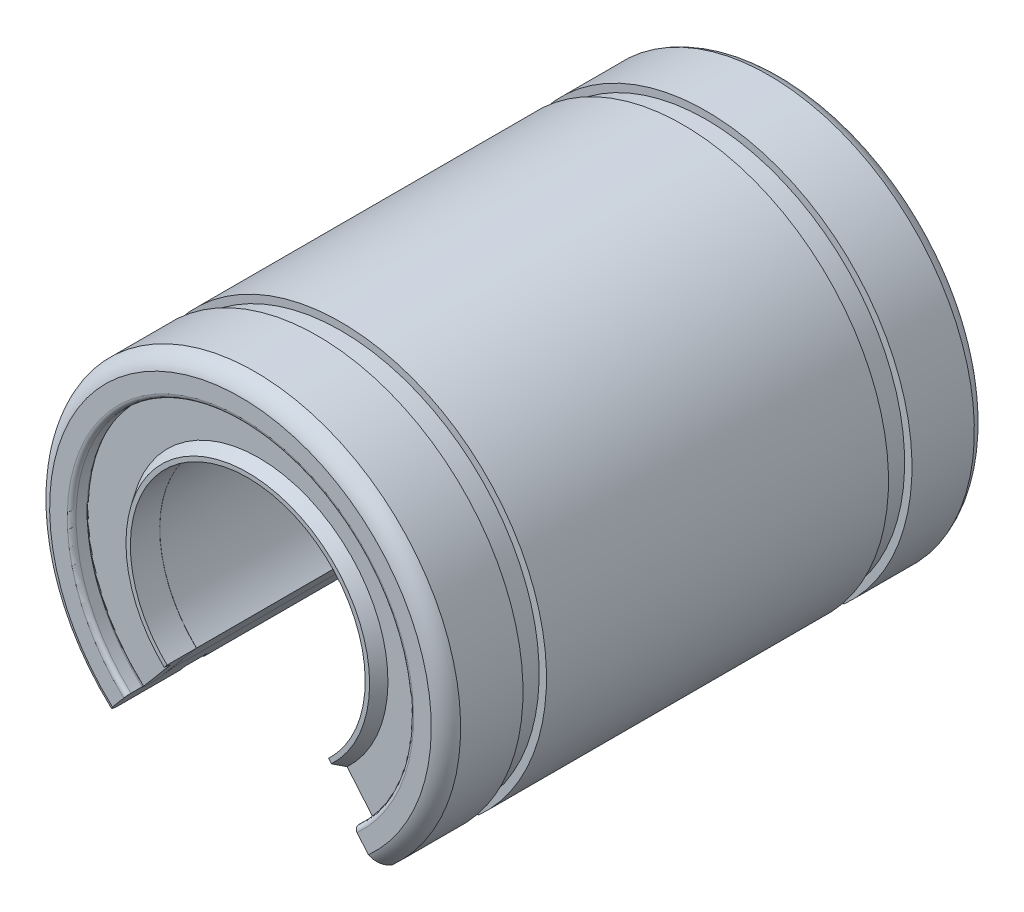
SolidWorks part; units mm, degrees
ref_plane "Спереди" through (0, 0, 0) normal (0, 0, 1) x (1, 0, 0)
ref_plane "Сверху" through (0, 0, 0) normal (0, 1, 0) x (1, 0, 0)
ref_plane "Справа" through (0, 0, 0) normal (1, 0, 0) x (0, 0, -1)
sketch "Эскиз1" plane through (0, 0, 0) normal (1, 0, 0) x (0, 0, -1)
  line L0 (-43.3432, 0) -> (33.9644, 0) construction
  line L1 (0, 8) -> (0, 0) construction
  line L2 (-18.5, 14) -> (18.5, 14)
  line L3 (-18.5, 14) -> (-18.5, 8)
  line L4 (-18.5, 8) -> (18.5, 8)
  line L5 (18.5, 14) -> (18.5, 8)
  line L6 (-11.65, 13.5) -> (11.65, 13.5) construction
  line L7 (-13.25, 14) -> (-11.65, 14)
  line L8 (-13.25, 14) -> (-13.25, 13.5)
  line L9 (-13.25, 13.5) -> (-11.65, 13.5)
  line L10 (-11.65, 14) -> (-11.65, 13.5)
  line L11 (11.65, 14) -> (13.25, 14)
  line L12 (11.65, 14) -> (11.65, 13.5)
  line L13 (11.65, 13.5) -> (13.25, 13.5)
  line L14 (13.25, 14) -> (13.25, 13.5)
  line L15 (0, 8) -> (0, 13.5) construction
  line L16 (-18.5, 11) -> (18.5, 11)
  line L17 (-17.25, 11.5) -> (-18.5, 11.5)
  line L18 (-17.25, 11) -> (-16, 11)
  line L19 (-17.25, 11) -> (-17.25, 12)
  line L20 (-17.25, 12) -> (-16, 12)
  line L21 (-16, 11) -> (-16, 12)
  line L22 (17.25, 11) -> (16, 11)
  line L23 (17.25, 11) -> (17.25, 12)
  line L24 (17.25, 12) -> (16, 12)
  line L25 (16, 11) -> (16, 12)
  line L26 (17.25, 11.5) -> (18.5, 11.5)
  line L27 (17.25, 11) -> (17.25, 8.8)
  line L28 (17.25, 8.8) -> (18, 8.3)
  line L29 (18, 8.3) -> (18, 8)
  line L30 (18, 8) -> (-18, 8)
  line L31 (-18, 8) -> (-18, 8.3)
  line L32 (-18, 8.3) -> (-17.25, 8.8)
  line L33 (-17.25, 8.8) -> (-17.25, 11)
  line L35 (16, 11) -> (15.99, 11)
  line L36 (16, 11) -> (16, 8)
  line L37 (16, 8) -> (15.99, 8)
  line L38 (15.99, 11) -> (15.99, 8)
  line L39 (-16, 11) -> (-15.99, 11)
  line L40 (-16, 11) -> (-16, 8)
  line L41 (-16, 8) -> (-15.99, 8)
  line L42 (-15.99, 11) -> (-15.99, 8)
  arc A0 (-18.5, 13) -> (-17.5, 14) centre (-17.0646, 12.5646) cw
  arc A1 (17.5, 14) -> (18.5, 13) centre (17.0646, 12.5646) cw
  arc A2 (15.7, 11) -> (16, 11.3) centre (15.7, 11.3) ccw
  arc A3 (16, 11.7) -> (16.3, 12) centre (16.3, 11.7) cw
  arc A4 (16.95, 12) -> (17.25, 11.7) centre (16.95, 11.7) cw
  arc A5 (17.25, 11.7) -> (17.45, 11.5) centre (17.45, 11.7) ccw
  arc A6 (18.2, 11.5) -> (18.5, 11.8) centre (18.2, 11.8) ccw
  arc A7 (-15.7, 11) -> (-16, 11.3) centre (-15.7, 11.3) cw
  arc A8 (-16, 11.7) -> (-16.3, 12) centre (-16.3, 11.7) ccw
  arc A9 (-16.95, 12) -> (-17.25, 11.7) centre (-16.95, 11.7) ccw
  arc A10 (-17.25, 11.7) -> (-17.45, 11.5) centre (-17.45, 11.7) cw
  arc A11 (-18.2, 11.5) -> (-18.5, 11.8) centre (-18.2, 11.8) cw
  dimension "D15" = 1.5
  dimension "D16" = 1.5
  dimension "D25" = 0.3
  dimension "D1" = 16
  dimension "D2" = 28
  dimension "D3" = 37
  dimension "D4" = 26.5
  dimension "D5" = 1.6
  dimension "D6" = 13.5
  dimension "D7" = 1.25
  dimension "D8" = 1.25
  dimension "D9" = 1
  dimension "D10" = 1
  dimension "D11" = 1.25
  dimension "D12" = 1.25
  dimension "D13" = 1
  dimension "D14" = 1
  dimension "D17" = 1
  dimension "D18" = 1
  dimension "D19" = 0.3
  dimension "D20" = 0.8
  dimension "D21" = 0.75
  dimension "D22" = 0.75
  dimension "D23" = 0.3
  dimension "D24" = 0.8
  dimension "D26" = 0.01
  dimension "D27" = 0.01
revolve "Повернуть1" add sketch "Эскиз1" angle 360 about L0 region at (0, 11.4862, 16.625) region at (0, 9.3805, 16.7185) region at (0, 9.5, 0) region at (0, 9.3805, -16.7185) region at (0, 11.4862, -16.625)
revolve "Повернуть2" add sketch "Эскиз1<3>" angle 360 about L0 region at (0, 12.513, 0) region at (0, 11.933, 17.183) region at (0, 11.933, 16.067) region at (0, 11.933, -17.183) region at (0, 11.933, -16.067)
sketch "Эскиз1<3>" plane through (0, 0, 0) normal (1, 0, 0) x (0, 0, -1) same geometry as "Эскиз1"
sketch "Эскиз2" plane through (0, 0, 0) normal (0, 0, 1) x (1, 0, 0)
  line L0 (0, 0) -> (0, 0.7452) construction
  line L1 (0, 0.7452) -> (12.3727, -14)
  line L2 (12.3727, -14) -> (-12.3727, -14)
  line L3 (-12.3727, -14) -> (0, 0.7452)
  line L4 (-5.5, -5.8095) -> (5.5, -5.8095) construction
  circle A0 centre (0, 0) radius 14 construction
  circle A1 centre (0, 0) radius 8 construction
  point P9 (0, 0)
  dimension "D1" = 80
  dimension "D2" = 11
extrude "Вырез-Вытянуть1" cut sketch "Эскиз2" against normal through all both and the other way through all
